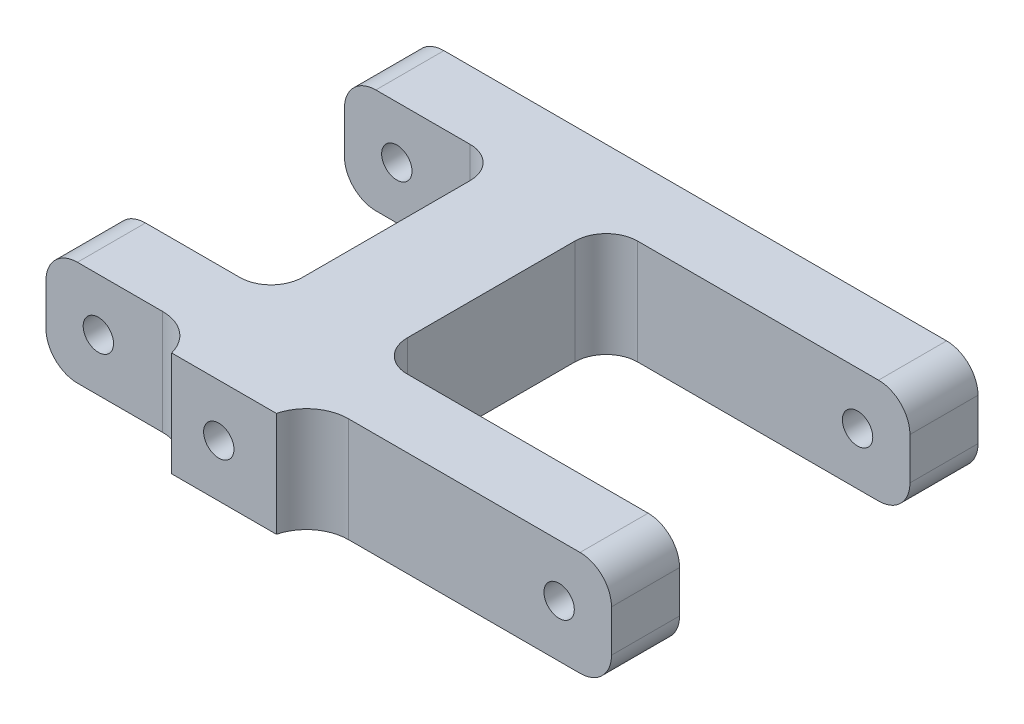
SolidWorks part; units mm, degrees
ref_plane "Front" through (0, 0, 0) normal (0, 0, 1) x (1, 0, 0)
ref_plane "Top" through (0, 0, 0) normal (0, 1, 0) x (1, 0, 0)
ref_plane "Right" through (0, 0, 0) normal (1, 0, 0) x (0, 0, -1)
sketch "Sketch1" plane through (0, 0, 0) normal (0, 1, 0) x (1, 0, 0)
  line L1 (0, 0) -> (54, 0)
  line L2 (0, 0) -> (0, -35)
  line L3 (0, -35) -> (54, -35)
  line L4 (54, 0) -> (54, -35)
  dimension "D1" = 35
  dimension "D2" = 54
extrude "Boss-Extrude1" add sketch "Sketch1" along normal blind 10
sketch "Sketch2" plane through (54, 0, 0) normal (1, 0, 0) x (0, 0, -1)
  line L0 (-35, 10) -> (0, 10) construction
  line L1 (-28.5, 10) -> (-6.5, 10)
  line L2 (-28.5, 10) -> (-28.5, 0)
  line L3 (-28.5, 0) -> (-6.5, 0)
  line L4 (-6.5, 10) -> (-6.5, 0)
  line L5 (-35, 0) -> (0, 0) construction
  line L6 (-35, 10) -> (-35, 0) construction
  line L7 (0, 10) -> (0, 0) construction
  dimension "D1" = 6.5
  dimension "D2" = 6.5
extrude "Cut-Extrude1" cut sketch "Sketch2" against normal blind 29
sketch "Sketch3" plane through (0, 0, 0) normal (-1, 0, 0) x (0, 0, 1)
  line L0 (0, 10) -> (35, 10) construction
  line L1 (6.5, 10) -> (28.5, 10)
  line L2 (6.5, 10) -> (6.5, 0)
  line L3 (6.5, 0) -> (28.5, 0)
  line L4 (28.5, 10) -> (28.5, 0)
  line L5 (0, 0) -> (35, 0) construction
  line L6 (35, 10) -> (35, 0) construction
  line L7 (0, 10) -> (0, 0) construction
  dimension "D1" = 6.5
  dimension "D2" = 6.5
extrude "Cut-Extrude2" cut sketch "Sketch3" against normal blind 15
sketch "Sketch5" plane through (0, 0, 35) normal (0, 0, 1) x (1, 0, 0)
  line L0 (0, 10) -> (54, 10) construction
  line L1 (0, 10) -> (0, 0) construction
  circle A0 centre (5, 5) radius 1.45
  circle A1 centre (49, 5) radius 1.45
  dimension "D1" = 2.9
  dimension "D2" = 5
  dimension "D3" = 5
  dimension "D4" = 2
extrude "Cut-Extrude4" cut sketch "Sketch5" against normal through all
fillet "Fillet1" radius 3 8 edges at (0, 0, 31.75) (0, 10, 31.75) (0, 0, 3.25) (0, 10, 3.25) (54, 10, 3.25) (54, 0, 3.25) (54, 0, 31.75) (54, 10, 31.75)
fillet "Fillet2" radius 3 4 edges at (25, 5, 28.5) (25, 5, 6.5) (15, 5, 28.5) (15, 5, 6.5)
sketch "Sketch8" plane through (0, 0, 35) normal (0, 0, 1) x (1, 0, 0)
  line L0 (3, 10) -> (51, 10) construction
  line L1 (15, 10) -> (25, 10)
  line L2 (15, 10) -> (15, 0)
  line L3 (15, 0) -> (25, 0)
  line L4 (25, 10) -> (25, 0)
  line L5 (3, 0) -> (51, 0) construction
  line L6 (54, 7) -> (54, 3) construction
  line L7 (0, 7) -> (0, 3) construction
  dimension "D1" = 29
  dimension "D2" = 15
extrude "Boss-Extrude2" add sketch "Sketch8" along normal blind 3
sketch "Sketch6" plane through (0, 0, 35) normal (0, 0, 1) x (1, 0, 0)
  line L0 (3, 10) -> (15, 10) construction
  line L2 (54, 7) -> (54, 3) construction
  circle A0 centre (19.5, 5) radius 1.45
  dimension "D1" = 2.9
  dimension "D2" = 5
  dimension "D3" = 34.5
extrude "Cut-Extrude5" cut sketch "Sketch6" against normal blind 15 and the other way blind 4
fillet "Fillet3" radius 4 2 edges at (25, 5, 35) (15, 5, 35)
equation "\"滑动-垂直孔\" = 0.6"
equation "\"滑动-水平孔\"= 0.3"
equation "\"松动-垂直孔\" = 0.3"
equation "\"松动-水平孔\"= 0.1"
equation "\"正常-垂直孔\" = 0.15"
equation "\"正常-水平孔\"= 0"
equation "\"紧缩-垂直孔\"= 0"
equation "\"紧缩-水平孔\"= - 0.1"
equation "\"D1@Sketch5\"=\"紧缩-水平孔\"+3"
equation "\"D1@Sketch6\"=\"紧缩-水平孔\"+3"
